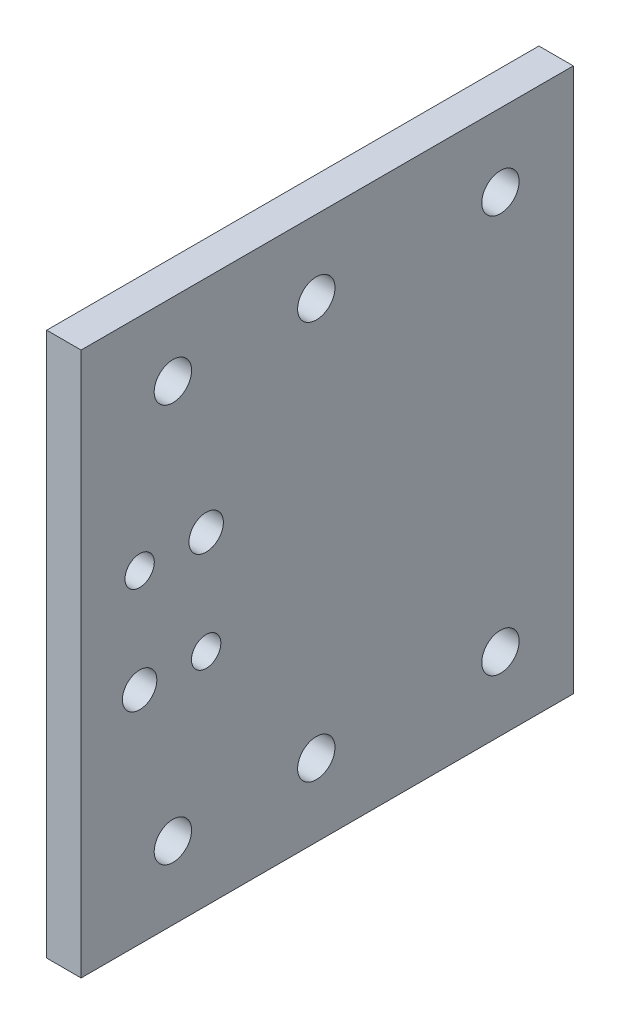
SolidWorks part; units mm, degrees
ref_plane "Front Plane" through (0, 0, 0) normal (1, 0, 0) x (0, 1, 0)
ref_plane "Top Plane" through (0, 0, 0) normal (0, 0, 1) x (0, 1, 0)
ref_plane "Right Plane" through (0, 0, 0) normal (0, 1, 0) x (-1, 0, 0)
sketch "Sketch1" plane through (0, 0, 0) normal (1, 0, 0) x (0, 1, 0)
  line L0 (0, 25) -> (0, -25) construction
  line L1 (-47.4, -25) -> (47.4, -25) construction
  line L2 (-47.4, -25) -> (-47.4, 25) construction
  line L3 (-47.4, 25) -> (47.4, 25) construction
  line L4 (47.4, -25) -> (47.4, 25) construction
  line L5 (-47.4, -25) -> (47.4, 25) construction
  line L6 (-47.4, 25) -> (47.4, -25) construction
  line L8 (-9, -5.8) -> (9, -5.8) construction
  line L9 (-9, -5.8) -> (-9, 5.8) construction
  line L10 (-9, 5.8) -> (9, 5.8) construction
  line L11 (9, -5.8) -> (9, 5.8) construction
  line L12 (-9, -5.8) -> (9, 5.8) construction
  line L13 (-9, 5.8) -> (9, -5.8) construction
  line L14 (-34.7, -15) -> (34.7, -15) construction
  line L15 (-34.7, -15) -> (-34.7, 15) construction
  line L16 (-34.7, 15) -> (34.7, 15) construction
  line L17 (34.7, -15) -> (34.7, 15) construction
  line L18 (-34.7, -15) -> (34.7, 15) construction
  line L19 (-34.7, 15) -> (34.7, -15) construction
  line L20 (-47.4, -25) -> (47.4, -25) construction
  line L21 (-47.4, -25) -> (-47.4, -69.8)
  line L22 (-47.4, -69.8) -> (47.4, -69.8)
  line L23 (47.4, -25) -> (47.4, -69.8) construction
  line L24 (-47.4, -69.8) -> (-34.7, -69.8) construction
  line L25 (-47.4, -69.8) -> (-47.4, -57.1) construction
  line L26 (-47.4, -57.1) -> (-34.7, -57.1) construction
  line L27 (-34.7, -69.8) -> (-34.7, -57.1) construction
  line L28 (47.4, -69.8) -> (34.7, -69.8) construction
  line L29 (47.4, -69.8) -> (47.4, -57.1) construction
  line L30 (47.4, -57.1) -> (34.7, -57.1) construction
  line L31 (34.7, -69.8) -> (34.7, -57.1) construction
  line L34 (47.4, -69.8) -> (47.4, 16)
  line L40 (-47.4, -25) -> (-47.4, 16)
  line L43 (-47.4, 16) -> (47.4, 16)
  line L44 (-47.4, -44.4) -> (47.4, -44.4) construction
  circle A0 centre (-9, 5.8) radius 3
  circle A1 centre (-9, -5.8) radius 2.555
  circle A2 centre (9, -5.8) radius 3
  circle A3 centre (9, 5.8) radius 2.555
  circle A4 centre (-34.7, 15) radius 2.555 construction
  circle A5 centre (-34.7, -15) radius 2.555 construction
  circle A6 centre (34.7, 15) radius 2.555 construction
  circle A7 centre (34.7, -15) radius 2.555 construction
  circle A8 centre (-34.7, -57.1) radius 3.2576
  circle A9 centre (34.7, -57.1) radius 3.2576
  circle A10 centre (-34.7, -25) radius 3.2576
  circle A11 centre (-34.7, 0) radius 3.2576
  circle A12 centre (34.7, 0) radius 3.2576
  circle A13 centre (34.7, -25) radius 3.2576
  point P0 (0, 0)
  point P8 (0, 0)
  point P17 (0, 0)
  point P48 (0, 0)
  point P49 (0, 0)
  dimension "D5" = 5.11
  dimension "D6" = 6
  dimension "D9" = 5.11
  dimension "D10" = 5.11
  dimension "D11" = 5.11
  dimension "D12" = 6
  dimension "D13" = 6
  dimension "D17" = 6.5151
  dimension "D20" = 10.2
  dimension "D1" = 11.6
  dimension "D2" = 18
  dimension "D3" = 94.8
  dimension "D4" = 50
  dimension "D7" = 12.7
  dimension "D8" = 30
  dimension "D14" = 38.6
  dimension "D15" = 12.7
  dimension "D16" = 12.7
  dimension "D19" = 25.4
extrude "Boss-Extrude1" add sketch "Sketch1" along normal blind 6
